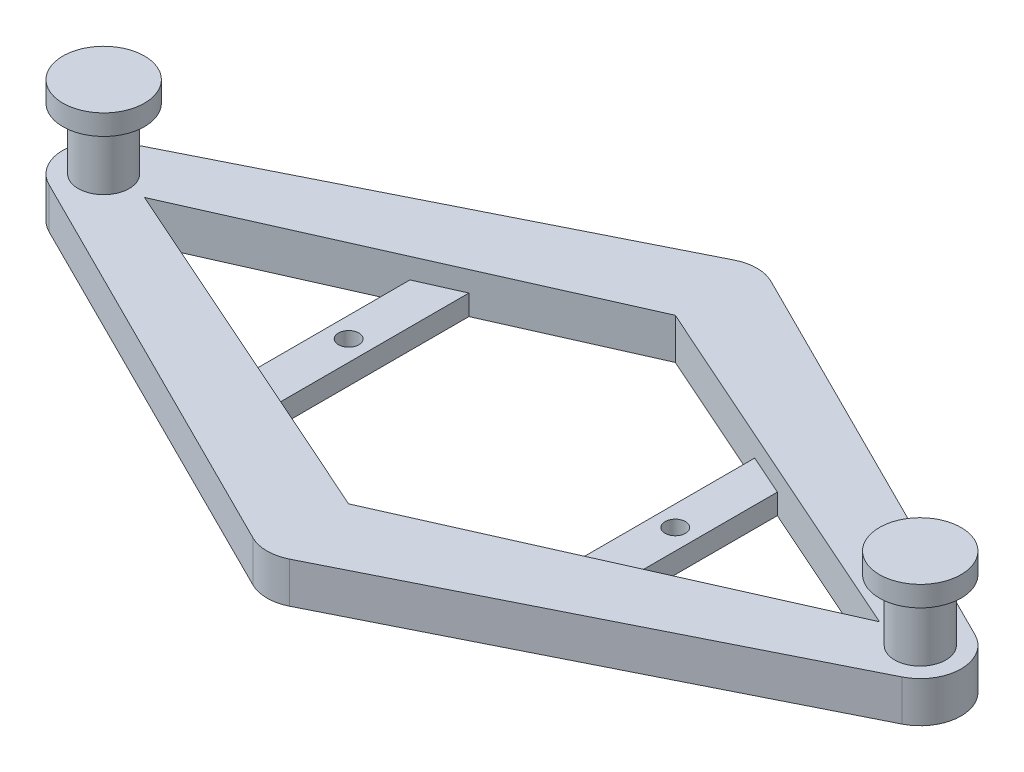
SolidWorks part; units mm, degrees
ref_plane "Front Plane" through (0, 0, 0) normal (0, 0, 1) x (1, 0, 0)
ref_plane "Top Plane" through (0, 0, 0) normal (0, 1, 0) x (1, 0, 0)
ref_plane "Right Plane" through (0, 0, 0) normal (1, 0, 0) x (0, 0, -1)
sketch "Sketch1" plane through (0, 0, 0) normal (0, 1, 0) x (1, 0, 0)
  line L0 (0, 0) -> (-50.8, 0)
  line L1 (0, 0) -> (50.8, 0)
  line L2 (0, 0) -> (0, 25.4)
  line L3 (0, 0) -> (0, -25.4)
  line L4 (-45.72, 0) -> (0, 20.32)
  line L5 (0, 20.32) -> (45.72, 0)
  line L6 (45.72, 0) -> (0, -20.32)
  line L7 (0, -20.32) -> (-45.72, 0)
  line L8 (-53.0718, -4.5437) -> (-2.2718, -29.9437)
  line L9 (-53.0718, 4.5437) -> (-2.2718, 29.9437)
  line L10 (2.2718, 29.9437) -> (53.0718, 4.5437)
  line L11 (53.0718, -4.5437) -> (2.2718, -29.9437)
  arc A0 (-53.0718, 4.5437) -> (-53.0718, -4.5437) centre (-50.8, 0) ccw
  arc A1 (2.2718, 29.9437) -> (-2.2718, 29.9437) centre (0, 25.4) ccw
  arc A2 (53.0718, -4.5437) -> (53.0718, 4.5437) centre (50.8, 0) ccw
  arc A3 (-2.2718, -29.9437) -> (2.2718, -29.9437) centre (0, -25.4) ccw
  dimension "D1" = 10.16
  dimension "D2" = 10.16
  dimension "D3" = 10.16
  dimension "D4" = 10.16
  dimension "D5" = 50.8
  dimension "D6" = 50.8
  dimension "D7" = 25.4
  dimension "D8" = 25.4
sketch "Sketch4" plane through (0, 0, 0) normal (0, 1, 0) x (1, 0, 0)
  line L0 (-22.86, 10.16) -> (-22.86, -10.16)
  line L1 (-45.72, 0) -> (0, 20.32) construction
  line L2 (0, -20.32) -> (-45.72, 0) construction
  line L3 (-22.86, 0) -> (-17.78, 0)
  line L4 (0, 0) -> (-50.8, 0) construction
  line L5 (-17.78, 0) -> (-17.78, 12.4178)
  line L6 (-17.78, 12.4178) -> (-17.78, -12.4178)
  line L7 (-22.86, 10.16) -> (-17.78, 12.4178)
  line L8 (-22.86, -10.16) -> (-17.78, -12.4178)
  line L9 (0, 20.32) -> (0, -20.32)
  line L10 (22.86, 10.16) -> (17.78, 12.4178)
  line L11 (22.86, 10.16) -> (22.86, -10.16)
  line L12 (22.86, -10.16) -> (17.78, -12.4178)
  line L13 (17.78, 12.4178) -> (17.78, -12.4178)
  circle A0 centre (-20.32, 0) radius 1.27
  circle A1 centre (20.32, 0) radius 1.27
sketch "Sketch5" plane through (0, 0, 0) normal (0, 1, 0) x (1, 0, 0)
  line L0 (-22.86, 10.16) -> (-22.86, -10.16)
  line L1 (-17.78, 12.4178) -> (-17.78, -12.4178)
  line L2 (-22.86, 10.16) -> (-17.78, 12.4178)
  line L3 (-22.86, -10.16) -> (-17.78, -12.4178)
  line L4 (22.86, 10.16) -> (17.78, 12.4178)
  line L5 (22.86, 10.16) -> (22.86, -10.16)
  line L6 (22.86, -10.16) -> (17.78, -12.4178)
  line L7 (17.78, 12.4178) -> (17.78, -12.4178)
  circle A0 centre (-20.32, 0) radius 1.27
  circle A1 centre (20.32, 0) radius 1.27
  point P2 (-22.86, 0)
extrude "Boss-Extrude2" add sketch "Sketch5" along normal blind 2.54
sketch "Sketch2" plane through (0, 0, 0) normal (0, 1, 0) x (1, 0, 0)
  line L0 (-45.72, 0) -> (0, 20.32)
  line L1 (0, 20.32) -> (45.72, 0)
  line L2 (45.72, 0) -> (0, -20.32)
  line L3 (0, -20.32) -> (-45.72, 0)
  line L4 (-53.0718, -4.5437) -> (-2.2718, -29.9437)
  line L5 (-53.0718, 4.5437) -> (-2.2718, 29.9437)
  line L6 (2.2718, 29.9437) -> (53.0718, 4.5437)
  line L7 (53.0718, -4.5437) -> (2.2718, -29.9437)
  arc A0 (-53.0718, 4.5437) -> (-53.0718, -4.5437) centre (-50.8, 0) ccw
  arc A1 (2.2718, 29.9437) -> (-2.2718, 29.9437) centre (0, 25.4) ccw
  arc A2 (53.0718, -4.5437) -> (53.0718, 4.5437) centre (50.8, 0) ccw
  arc A3 (-2.2718, -29.9437) -> (2.2718, -29.9437) centre (0, -25.4) ccw
extrude "Boss-Extrude1" add sketch "Sketch2" along normal blind 5.08
sketch "Sketch6" plane through (0, 5.08, 0) normal (0, 1, 0) x (1, 0, 0)
  circle A0 centre (-50.8, 0) radius 3.175
  circle A1 centre (50.8, 0) radius 3.175
extrude "Boss-Extrude3" add sketch "Sketch6" along normal blind 7.62
sketch "Sketch10" plane through (0, 12.7, 0) normal (0, 1, 0) x (1, 0, 0)
  circle A0 centre (-50.8, 0) radius 5.08
sketch "Sketch11" plane through (0, 12.7, 0) normal (0, 1, 0) x (1, 0, 0)
  circle A0 centre (-50.8, 0) radius 5.08
extrude "Boss-Extrude4" add sketch "Sketch11" along normal blind 2.54
sketch "Sketch12" plane through (0, 12.7, 0) normal (0, 1, 0) x (1, 0, 0)
  circle A0 centre (50.8, 0) radius 5.08
sketch "Sketch13" plane through (0, 12.7, 0) normal (0, 1, 0) x (1, 0, 0)
  circle A0 centre (50.8, 0) radius 5.08
extrude "Boss-Extrude5" add sketch "Sketch13" along normal blind 2.54
